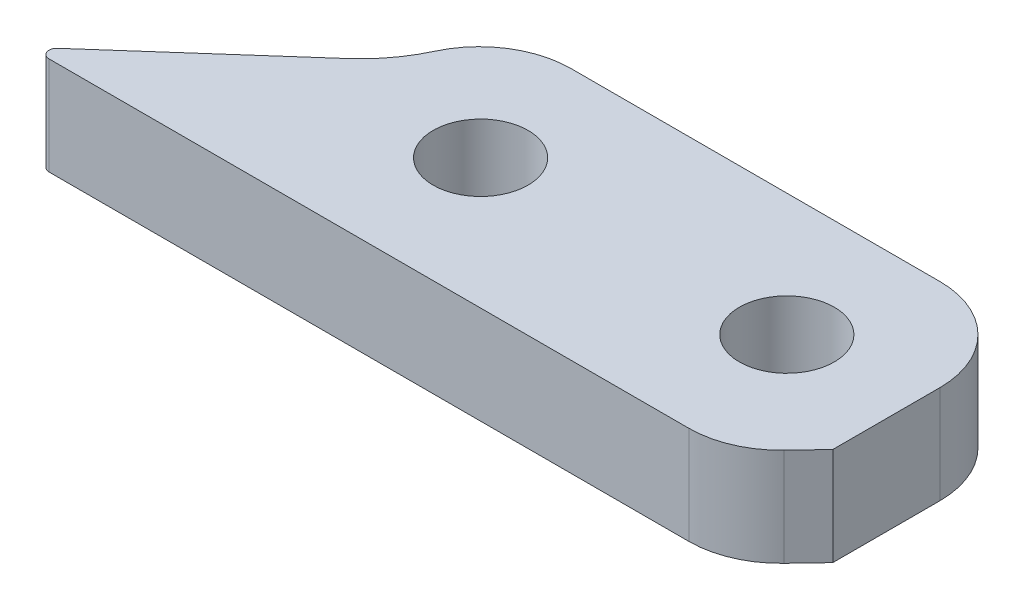
SolidWorks part; units mm, degrees
material "Titanium Ti-8Mn, Annealed"
ref_plane "Front Plane" through (0, 0, 0) normal (0, 0, 1) x (1, 0, 0)
ref_plane "Top Plane" through (0, 0, 0) normal (0, 1, 0) x (1, 0, 0)
ref_plane "Right Plane" through (0, 0, 0) normal (1, 0, 0) x (0, 0, -1)
sketch "Sketch1" plane through (0, 0, 0) normal (0, 1, 0) x (1, 0, 0)
  line L5 (36, -13) -> (36, 0)
  line L6 (36, 0) -> (0, 0)
  line L8 (36, -13) -> (32.6676, -16.5)
  line L9 (32.6676, -16.5) -> (-1.4555, -16.5)
  line L10 (0, 0) -> (0, -5)
  line L11 (0, -5) -> (-13, -16.5)
  line L12 (-13, -16.5) -> (-1.4555, -16.5)
  circle A0 centre (28, -8) radius 3.1
  circle A1 centre (8, -8) radius 3.1
  point P1 (0, 0)
  dimension "D8" = 6.2
  dimension "D9" = 6.2
  dimension "D1" = 13
  dimension "D2" = 36
  dimension "D3" = 8
  dimension "D4" = 13
  dimension "D5" = 5
  dimension "D6" = 8.5
  dimension "D10" = 20
  dimension "D11" = 8
extrude "Boss-Extrude1" add sketch "Sketch1" along normal blind 6.4
fillet "Fillet1" radius 6 3 edges at (32.6676, 3.2, 16.5) (36, 3.2, 0) (0, 3.2, 0)
fillet "Fillet2" radius 10 1 edges at (0, 3.2, 5)
fillet "Fillet3" radius 0.5 1 edges at (-13, 3.2, 16.5)
